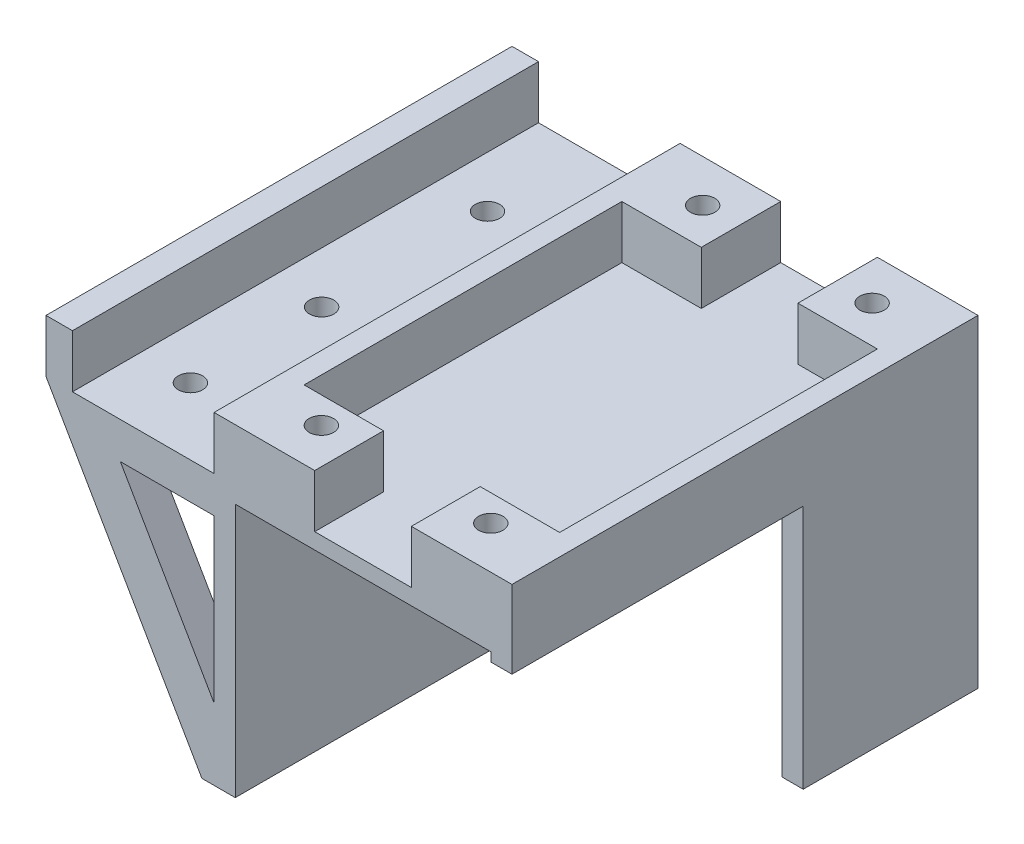
SolidWorks part; units mm, degrees
ref_plane "Front" through (0, 0, 0) normal (0, 0, 1) x (1, 0, 0)
ref_plane "Top" through (0, 0, 0) normal (0, 1, 0) x (1, 0, 0)
ref_plane "Right" through (0, 0, 0) normal (1, 0, 0) x (0, 0, -1)
sketch "Sketch1" plane through (0, 0, 0) normal (0, 0, 1) x (1, 0, 0)
  line L0 (0, 0) -> (0, 70)
  line L1 (0, 70) -> (56.254, 70)
  line L2 (56.254, 70) -> (56.254, 0)
  line L3 (56.254, 0) -> (52.254, 0)
  line L4 (52.254, 0) -> (52.254, 65)
  line L5 (52.254, 65) -> (4, 65)
  line L6 (4, 65) -> (4, 0)
  line L7 (4, 0) -> (0, 0)
  line L9 (4, 55) -> (52.254, 55)
  line L10 (4, 55) -> (4, 52)
  line L11 (4, 52) -> (52.254, 52)
  line L12 (52.254, 55) -> (52.254, 52)
  dimension "D1" = 48.254
  dimension "D2" = 4
  dimension "D3" = 4
  dimension "D4" = 5
  dimension "D5" = 70
  dimension "D6" = 3
  dimension "D7" = 10
extrude "Boss-Extrude1" add sketch "Sketch1" along normal blind 70 contours L7 L6 L5 L4 L3 L2 L1 L0 | L9 L12 L11 L10 region at (0.898, 35, 0)
sketch "Sketch3" plane through (0, 0, 70) normal (0, 0, 1) x (1, 0, 0)
  line L0 (0, 70) -> (-40.3946, 70)
  line L1 (-40.3946, 70) -> (0, 0.0344)
  line L2 (0, 0) -> (0, 70) construction
  line L3 (0, 0.0344) -> (0, 70)
  line L4 (0, 70) -> (0, 62.5)
  line L5 (0, 62.5) -> (-26, 62.5)
  line L6 (-26, 62.5) -> (0, 17.4667)
  line L7 (0, 17.4667) -> (0, 0.0344)
  line M11 (0, 70) -> (0, 0)
  dimension "D1" = 60
  dimension "D2" = 180
  dimension "D3" = 7.5
  dimension "D4" = 26
extrude "Boss-Extrude3" add sketch "Sketch3" against normal blind 8 contours L6 L5 L0 L1 M11 region at (-16.8587, 46.1047, 70)
sketch "Sketch4" plane through (0, 0, 0) normal (0, 0, -1) x (-1, 0, 0)
  line L0 (0, 70) -> (40.3946, 70)
  line L1 (40.3946, 70) -> (0, 0)
  line L2 (0, 0) -> (0, 17.4667)
  line L3 (0, 17.4667) -> (26, 62.5)
  line L4 (26, 62.5) -> (0, 62.5)
  line L5 (0, 62.5) -> (0, 70)
extrude "Boss-Extrude4" add sketch "Sketch4" against normal blind 8
ref_plane "Plane1" through (0, 0, 39) normal (0, 0, -1) x (-1, 0, 0)
sketch "Sketch5" plane through (0, 0, 39) normal (0, 0, -1) x (-1, 0, 0)
  line L0 (0, 62.5) -> (0, 70)
  line L1 (0, 70) -> (40.3946, 70)
  line L2 (40.3946, 70) -> (0, 0)
  line L3 (0, 0) -> (0, 17.4667)
  line L4 (0, 17.4667) -> (26, 62.5)
  line L5 (26, 62.5) -> (0, 62.5)
extrude "Boss-Extrude5" add sketch "Sketch5" along normal blind 8
sketch "Sketch6" plane through (0, 0, 0) normal (0, 0, -1) x (-1, 0, 0)
  line L5 (0, 62.5) -> (36.0666, 62.5)
  line L6 (0, 0) -> (40.3946, 70) construction
  line L7 (36.0666, 62.5) -> (40.3946, 70)
  line L8 (40.3946, 70) -> (0, 70)
  line L9 (40.3946, 70) -> (-56.254, 70) construction
  line L10 (0, 70) -> (0, 62.5)
  line L11 (-4, 0) -> (0, 0)
  line L12 (0, 0) -> (7.5019, 13)
  line L13 (7.5019, 13) -> (-4, 13)
  line L14 (-4, 52) -> (-4, 0) construction
  line L15 (-4, 13) -> (-4, 0)
  dimension "D1" = 13
extrude "Boss-Extrude6" add sketch "Sketch6" against normal blind 70
sketch "Sketch7" plane through (0, 0, 70) normal (0, 0, 1) x (1, 0, 0)
  line L0 (0, 17.4667) -> (0, 62.5) construction
  line L1 (-40.3946, 70) -> (0, 70)
  line L2 (-40.3946, 70) -> (-40.3946, 53)
  line L3 (-40.3946, 53) -> (0, 53)
  line L4 (0, 70) -> (0, 53)
  dimension "D1" = 17
extrude "Cut-Extrude3" cut sketch "Sketch7" against normal blind 70
sketch "Sketch8" plane through (0, 0, 0) normal (0, 0, -1) x (-1, 0, 0)
  line L1 (-4, 55) -> (-4, 52)
  line L2 (-4, 52) -> (-52.254, 52) construction
  line L3 (-4, 52) -> (30.0074, 52)
  line L4 (0, 0) -> (30.5845, 53) construction
  line L6 (30.0074, 52) -> (31.7386, 55)
  line L7 (31.7386, 55) -> (-4, 55)
  dimension "D1" = 180
extrude "Boss-Extrude7" add sketch "Sketch8" against normal blind 70
sketch "Sketch11" plane through (0, 0, 70) normal (0, 0, 1) x (1, 0, 0)
  line L0 (-31.7386, 55) -> (0, 0)
  line L3 (-31.7386, 55) -> (0, 55) construction
  line L4 (-27.289, 55) -> (-31.7386, 55)
  line L5 (-27.289, 55) -> (-3.0537, 13)
  line L6 (-3.0537, 13) -> (0, 0)
extrude "Boss-Extrude10" add sketch "Sketch11" against normal blind 8
sketch "Sketch12" plane through (0, 0, 70) normal (0, 0, 1) x (1, 0, 0)
  line L0 (-31.7386, 55) -> (-27.7598, 48.1051)
  line L1 (0, 0) -> (-31.7386, 55) construction
  line L2 (-27.7598, 48.1051) -> (0, 48.1051)
  line L3 (0, 17.4667) -> (0, 52) construction
  line L4 (0, 48.1051) -> (0, 55)
  line L5 (0, 55) -> (-31.7386, 55)
extrude "Boss-Extrude11" add sketch "Sketch12" against normal blind 70
sketch "Sketch13" plane through (0, 0, 0) normal (0, -1, 0) x (1, 0, 0)
  line L1 (67.4394, -10.6205) -> (-15.562, -10.6205)
  line L2 (67.4394, -10.6205) -> (67.4394, 77.2481)
  line L3 (67.4394, 77.2481) -> (-15.562, 77.2481)
  line L4 (-15.562, -10.6205) -> (-15.562, 77.2481)
extrude "Cut-Extrude4" cut sketch "Sketch13" against normal blind 4
sketch "Sketch14" plane through (0, 0, 70) normal (0, 0, 1) x (1, 0, 0)
  line L0 (-2.3083, 4) -> (-31.7386, 55)
  line L1 (-31.7386, 55) -> (0, 55)
  line L2 (0, 55) -> (0, 70)
  line L3 (0, 70) -> (56.254, 70)
  line L4 (56.254, 70) -> (56.254, 4)
  line L5 (56.254, 4) -> (52.254, 4)
  line L6 (52.254, 4) -> (52.254, 52)
  line L7 (52.254, 52) -> (4, 52)
  line L8 (4, 52) -> (4, 4)
  line L9 (4, 4) -> (-2.3083, 4)
  line L14 (-17.6891, 48.1051) -> (0, 48.1051)
  line L15 (52.254, 55) -> (4, 55)
  line L16 (52.254, 55) -> (52.254, 65)
  line L17 (52.254, 65) -> (4, 65)
  line L18 (4, 55) -> (4, 65)
  line L19 (-17.6891, 48.1051) -> (0, 48.1051) construction
  line L20 (0, 48.1051) -> (0, 17.4667)
  line L21 (0, 17.4667) -> (-17.6891, 48.1051)
extrude "Boss-Extrude12" add sketch "Sketch14" along normal blind 20
sketch "Sketch15" plane through (0, 0, 90) normal (0, 0, 1) x (1, 0, 0)
  line L0 (56.254, 4) -> (56.254, 70) construction
  line L1 (56.254, 65) -> (37.264, 65)
  line L2 (56.254, 65) -> (56.254, 55)
  line L3 (56.254, 55) -> (37.264, 55)
  line L4 (37.264, 65) -> (37.264, 55)
  line L5 (4, 55) -> (52.254, 55) construction
  dimension "D1" = 18.99
sketch "Sketch16" plane through (0, 0, 90) normal (0, 0, 1) x (1, 0, 0)
  line L1 (0, 70) -> (56.254, 70)
  line L2 (0, 70) -> (0, 65)
  line L3 (0, 65) -> (56.254, 65)
  line L4 (56.254, 70) -> (56.254, 65)
extrude "Cut-Extrude5" cut sketch "Sketch16" against normal blind 100
sketch "Sketch17" plane through (0, 65, 0) normal (0, 1, 0) x (1, 0, 0)
  line L1 (52.254, 0) -> (37.254, 0)
  line L2 (52.254, 0) -> (52.254, -15)
  line L3 (52.254, -15) -> (37.254, -15)
  line L4 (37.254, 0) -> (37.254, -15)
  line L5 (52.254, -90) -> (37.254, -90)
  line L6 (52.254, -90) -> (52.254, -75)
  line L7 (52.254, -75) -> (37.254, -75)
  line L8 (37.254, -90) -> (37.254, -75)
  dimension "D1" = 15
  dimension "D2" = 15
  dimension "D3" = 15
  dimension "D4" = 15
extrude "Boss-Extrude14" add sketch "Sketch17" against normal blind 13
sketch "Sketch21" plane through (0, 52, 0) normal (0, -1, 0) x (-1, 0, 0)
  circle A0 centre (-44.254, -80) radius 2.3
  circle A1 centre (-44.254, -8) radius 2.3
sketch "Sketch22" plane through (0, 52, 0) normal (0, -1, 0) x (1, 0, 0)
  line L1 (48.0965, 6.0036) -> (47.9041, 10.3295)
  line L2 (47.9041, 10.3295) -> (44.0617, 12.3259)
  line L3 (44.0617, 12.3259) -> (40.4115, 9.9964)
  line L4 (40.4115, 9.9964) -> (40.6039, 5.6705)
  line L5 (40.6039, 5.6705) -> (44.4463, 3.6741)
  line L6 (44.4463, 3.6741) -> (48.0965, 6.0036)
  line L7 (45.2007, 75.7746) -> (48.3866, 78.7072)
  line L8 (48.3866, 78.7072) -> (47.4399, 82.9325)
  line L9 (47.4399, 82.9325) -> (43.3073, 84.2254)
  line L10 (43.3073, 84.2254) -> (40.1214, 81.2928)
  line L11 (40.1214, 81.2928) -> (41.0681, 77.0675)
  line L12 (41.0681, 77.0675) -> (45.2007, 75.7746)
  circle A0 centre (44.254, 8) radius 3.75 construction
  circle A1 centre (44.254, 80) radius 3.75 construction
  point P10 (42.2366, 11.1611)
  dimension "D1" = 7.5
  dimension "D2" = 7.5
extrude "Cut-Extrude8" cut sketch "Sketch22" against normal blind 5
extrude "Cut-Extrude9" cut sketch "Sketch21" against normal blind 15
sketch "Sketch23" plane through (0, 0, 0) normal (-0.8661, -0.4998, 0) x (0, 0, 1)
  line L0 (90, 63.5007) -> (90, 4.6182) construction
  line L1 (70, 55.5401) -> (82, 55.5401)
  line L2 (70, 55.5401) -> (70, 15.0093)
  line L3 (70, 15.0093) -> (82, 15.0093)
  line L4 (82, 55.5401) -> (82, 15.0093)
  line L5 (62, 55.5401) -> (62, 15.0093) construction
  dimension "D1" = 8
  dimension "D2" = 8
extrude "Cut-Extrude10" cut sketch "Sketch23" against normal blind 9
sketch "Sketch25" plane through (0, 48.1051, 0) normal (0, -1, 0) x (-1, 0, 0)
  circle A0 centre (17.0755, -19.3006) radius 2.3
  circle A1 centre (17.0755, -50.6137) radius 2.3
extrude "Cut-Extrude11" cut sketch "Sketch25" against normal blind 20
sketch "Sketch26" plane through (0, 48.1051, 0) normal (0, -1, 0) x (1, 0, 0)
  circle A0 centre (-17.0755, 75.3913) radius 2.3
extrude "Cut-Extrude12" cut sketch "Sketch26" against normal blind 20
sketch "Sketch27" plane through (0, 0, 90) normal (0, 0, 1) x (1, 0, 0)
  line L0 (-23.3104, 48.1051) -> (-27.7598, 48.1051)
  line L1 (-31.7386, 55) -> (-2.3083, 4) construction
  line L2 (-27.7598, 48.1051) -> (-31.7386, 55)
  line L3 (-31.7386, 55) -> (-23.3104, 55)
  line L4 (0, 55) -> (-31.7386, 55) construction
  line L5 (-23.3104, 55) -> (-23.3104, 48.1051)
extrude "Boss-Extrude16" add sketch "Sketch27" against normal blind 20
sketch "Sketch28" plane through (0, 55, 0) normal (0, 1, 0) x (1, 0, 0)
  line L0 (4, -90) -> (37.254, -90) construction
  line L1 (4, 0) -> (19, 0)
  line L2 (4, 0) -> (4, -15)
  line L3 (4, -15) -> (19, -15)
  line L4 (19, 0) -> (19, -15)
  line L5 (4, -90) -> (19, -90)
  line L6 (4, -90) -> (4, -75)
  line L7 (4, -75) -> (19, -75)
  line L8 (19, -90) -> (19, -75)
  line L9 (4, 0) -> (4, -90) construction
  dimension "D1" = 15
  dimension "D2" = 15
  dimension "D3" = 15
  dimension "D4" = 15
extrude "Boss-Extrude17" add sketch "Sketch28" along normal blind 10
sketch "Sketch29" plane through (0, 52, 0) normal (0, -1, 0) x (-1, 0, 0)
  circle A0 centre (-12.254, -8) radius 2.3
  circle A1 centre (-12.254, -80) radius 2.3
extrude "Cut-Extrude13" cut sketch "Sketch29" against normal blind 20
sketch "Sketch30" plane through (0, 48.1051, 0) normal (0, -1, 0) x (1, 0, 0)
  line L1 (-27.7598, 70) -> (-17.3688, 70)
  line L2 (-27.7598, 70) -> (-27.7598, 82)
  line L3 (-27.7598, 82) -> (-17.3688, 82)
  line L4 (-17.3688, 70) -> (-17.3688, 82)
extrude "Boss-Extrude18" add sketch "Sketch30" against normal blind 5
sketch "Sketch31" plane through (0, 48.1051, 0) normal (0, -1, 0) x (1, 0, 0)
  circle A0 centre (-17.0755, 75.3913) radius 2.3
extrude "Cut-Extrude14" cut sketch "Sketch31" against normal blind 45
sketch "Sketch33" plane through (0, 55, 0) normal (0, 1, 0) x (1, 0, 0)
  circle A0 centre (27.6164, -46.5233) radius 1
  circle A1 centre (26.8974, -20.9206) radius 1
  circle A2 centre (28.9102, -66.6327) radius 1
  circle A3 centre (-20.9687, -5.2719) radius 1
  circle A4 centre (-23.4497, -23.5026) radius 1
  circle A5 centre (-17.8546, -42.0102) radius 1
  circle A6 centre (-22.4497, -64.7625) radius 1
  circle A7 centre (-17.8546, -85.6157) radius 1
ref_plane "Plane2" through (-31.7386, 55, 90) normal (0.4998, -0.8661, 0) x (-0.8661, -0.4998, 0)
sketch "Sketch36" plane through (0, 0, 90) normal (0, 0, 1) x (1, 0, 0)
  circle A0 centre (23.0361, 36.9328) radius 60.0365
extrude "Cut-Extrude15" cut sketch "Sketch36" against normal blind 2
sketch "Sketch37" plane through (0, 55, 0) normal (0, 1, 0) x (1, 0, 0)
  line L0 (-31.7386, -88) -> (0, -88) construction
  line L1 (-31.7386, 0) -> (-26.7386, 0)
  line L2 (-31.7386, 0) -> (-31.7386, -88)
  line L3 (-31.7386, -88) -> (-26.7386, -88)
  line L4 (-26.7386, 0) -> (-26.7386, -88)
  dimension "D1" = 5
extrude "Boss-Extrude19" add sketch "Sketch37" along normal blind 10
sketch "Sketch38" plane through (0, 52, 0) normal (0, -1, 0) x (1, 0, 0)
  line L1 (12.254, 75.6699) -> (16.004, 77.8349)
  line L2 (16.004, 77.8349) -> (16.004, 82.1651)
  line L3 (16.004, 82.1651) -> (12.254, 84.3301)
  line L4 (12.254, 84.3301) -> (8.504, 82.1651)
  line L5 (8.504, 82.1651) -> (8.504, 77.8349)
  line L6 (8.504, 77.8349) -> (12.254, 75.6699)
  line L7 (15.5673, 5.2122) -> (16.325, 9.4755)
  line L8 (16.325, 9.4755) -> (13.0117, 12.2633)
  line L9 (13.0117, 12.2633) -> (8.9407, 10.7878)
  line L10 (8.9407, 10.7878) -> (8.183, 6.5245)
  line L11 (8.183, 6.5245) -> (11.4963, 3.7367)
  line L12 (11.4963, 3.7367) -> (15.5673, 5.2122)
  circle A0 centre (12.254, 80) radius 3.75 construction
  circle A1 centre (12.254, 8) radius 3.75 construction
  dimension "D1" = 7.5
  dimension "D2" = 7.5
extrude "Cut-Extrude16" cut sketch "Sketch38" against normal blind 5
sketch "Sketch39" plane through (4, 0, 0) normal (1, 0, 0) x (0, 0, -1)
  circle A0 centre (-47.5147, 36.4853) radius 2.1
  circle A1 centre (-48, 20) radius 2.1
  circle A2 centre (-16.4853, 19.5147) radius 2.1
  circle A3 centre (-16.4853, 36.4853) radius 2.1
extrude "Cut-Extrude17" cut sketch "Sketch39" against normal blind 5
sketch "Sketch40" plane through (56.254, 0, 0) normal (1, 0, 0) x (0, 0, -1)
  line L0 (-88, 50.3083) -> (-33, 50.3083)
  line L1 (-88, 65) -> (-88, 4) construction
  line L2 (-88, 50.3083) -> (-88, 4)
  line L3 (-88, 4) -> (-33, 4)
  line L4 (-88, 4) -> (0, 4) construction
  line L5 (-33, 4) -> (-33, 50.3083)
  dimension "D1" = 55
extrude "Cut-Extrude18" cut sketch "Sketch40" against normal blind 5
